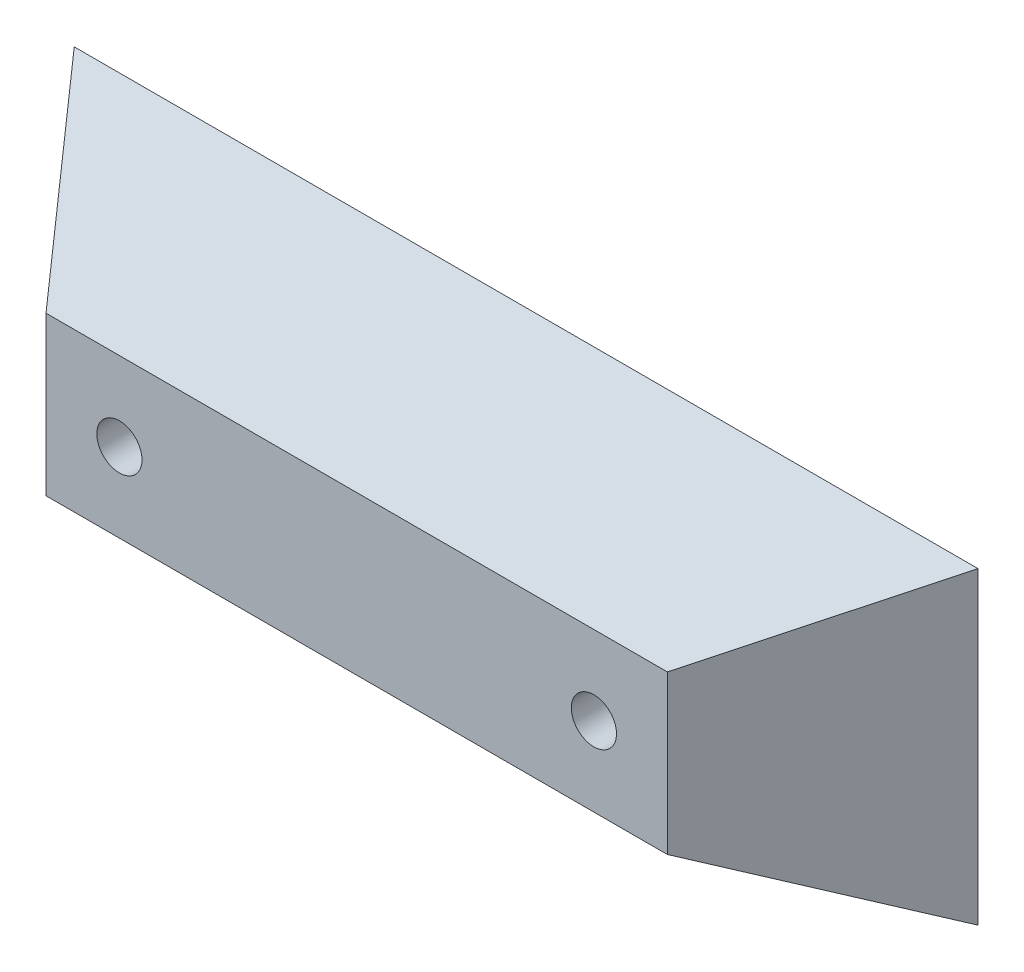
SolidWorks part; units mm, degrees
ref_plane "Płaszczyzna przednia" through (0, 0, 0) normal (0, 0, 1) x (1, 0, 0)
ref_plane "Płaszczyzna górna" through (0, 0, 0) normal (0, 1, 0) x (1, 0, 0)
ref_plane "Płaszczyzna prawa" through (0, 0, 0) normal (1, 0, 0) x (0, 0, -1)
sketch "Szkic1" plane through (0, 0, 0) normal (0, 1, 0) x (1, 0, 0)
  line L0 (-40, 0) -> (-27.5, -15)
  line L1 (-27.5, -15) -> (27.5, -15)
  line L2 (27.5, -15) -> (40, 0)
  line L3 (40, 0) -> (-40, 0)
  point P2 (0, 0)
  point P5 (0, 0)
  point P6 (0, 0)
extrude "Dodanie-wyciągnięcie1" add sketch "Szkic1" along normal blind 30
sketch "Szkic2" plane through (0, 0, 0) normal (0, 0, -1) x (-1, 0, 0)
  circle A0 centre (-21, 15) radius 2
  circle A1 centre (21, 15) radius 2
extrude "Wytnij-wyciągnięcie1" cut sketch "Szkic2" against normal up to next
chamfer "Sfazowanie1" distance 18 distance2 8 1 edges at (0, 0, 15) first distance on face at (0, 0, 7.5)
chamfer "Sfazowanie2" distance 8 distance2 18 1 edges at (0, 30, 15) first distance on face at (19, 15, 15)
